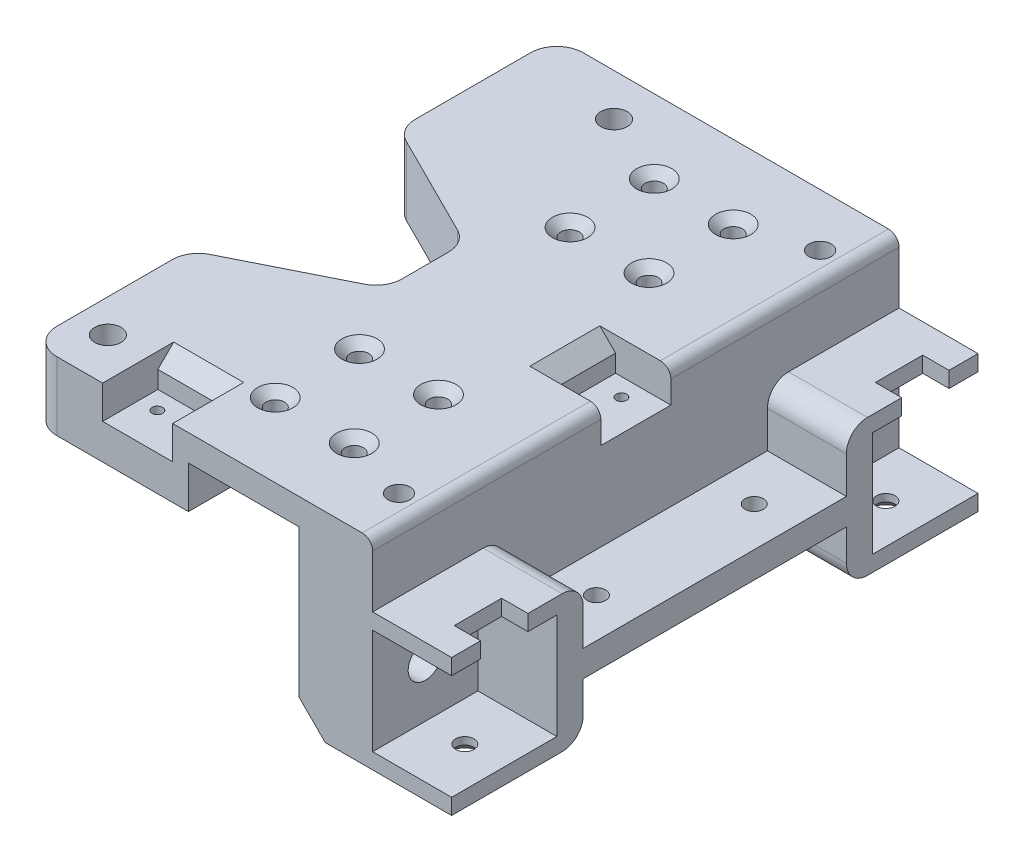
SolidWorks part; units mm, degrees
ref_plane "Front Plane" through (0, 0, 0) normal (0, 0, 1) x (1, 0, 0)
ref_plane "Top Plane" through (0, 0, 0) normal (0, 1, 0) x (1, 0, 0)
ref_plane "Right Plane" through (0, 0, 0) normal (1, 0, 0) x (0, 0, -1)
sketch "Sketch1" plane through (0, 0, 0) normal (0, 1, 0) x (1, 0, 0)
  line L0 (0, 50) -> (0, -50) construction
  line L1 (-10, 50) -> (10, 50)
  line L2 (-10, 50) -> (-10, -50)
  line L3 (-10, -50) -> (10, -50)
  line L4 (10, 50) -> (10, -50) construction
  line L5 (-10, 50) -> (10, -50) construction
  line L6 (-10, -50) -> (10, 50) construction
  line L7 (-7.5, 36) -> (7.5, 36) construction
  line L8 (-7.5, 36) -> (7.5, 20) construction
  line L9 (-10, 0) -> (10, 0) construction
  line L10 (-7.5, -36) -> (7.5, -20) construction
  line L11 (-7.5, -36) -> (7.5, -36) construction
  line L12 (-7.5, 20) -> (7.5, 20) construction
  line L13 (10, 50) -> (11, 50)
  line L14 (11, 50) -> (11, -50)
  line L15 (11, -50) -> (10, -50)
  circle A0 centre (-7.5, 36) radius 1.75
  circle A1 centre (7.5, 36) radius 1.75
  circle A2 centre (-7.5, 20) radius 1.75
  circle A3 centre (7.5, 20) radius 1.75
  circle A4 centre (7.5, -20) radius 1.75
  circle A5 centre (-7.5, -20) radius 1.75
  circle A6 centre (7.5, -36) radius 1.75
  circle A7 centre (-7.5, -36) radius 1.75
  point P0 (0, 0)
  point P16 (0, 36)
  dimension "D2" = 3.5
  dimension "D1" = 20
  dimension "D3" = 15
  dimension "D4" = 16
  dimension "D5" = 100
  dimension "D6" = 20
  dimension "D7" = 1
extrude "Boss-Extrude1" add sketch "Sketch1" along normal blind 5
sketch "Sketch2" plane through (11, 0, 0) normal (1, 0, 0) x (0, 0, -1)
  line L1 (-50, 5) -> (50, 5)
  line L2 (-50, 5) -> (-50, -33)
  line L3 (-50, -33) -> (50, -33)
  line L5 (50, 5) -> (50, -33)
  line L6 (50, 5) -> (50, 0) construction
  line L7 (-50, 5) -> (-50, 0) construction
  line L8 (-50, 5) -> (50, 5) construction
  dimension "D1" = 38
extrude "Boss-Extrude2" add sketch "Sketch2" along normal blind 14
sketch "Sketch3" plane through (25, 0, 0) normal (1, 0, 0) x (0, 0, -1)
  line L0 (0, 5) -> (0, -33) construction
  line L1 (-25, -18) -> (25, -18)
  line L2 (-25, -18) -> (-25, -23)
  line L3 (-25, -23) -> (25, -23)
  line L4 (25, -18) -> (25, -23)
  line L5 (50, 5) -> (-50, 5) construction
  line L6 (-50, -33) -> (50, -33) construction
  point P10 (0, -18)
  dimension "D1" = 5
  dimension "D2" = 50
  dimension "D3" = 10
extrude "Boss-Extrude3" add sketch "Sketch3" along normal blind 15
sketch "Sketch4" plane through (0, -18, 0) normal (0, 1, 0) x (1, 0, 0)
  line L0 (25, 0) -> (40, 0) construction
  line L1 (25, 25) -> (25, -25) construction
  line L2 (40, 25) -> (40, -25) construction
  line L3 (32.5, -15) -> (32.5, 15) construction
  circle A0 centre (32.5, 15) radius 1.75
  circle A1 centre (32.5, -15) radius 1.75
  point P8 (32.5, 0)
  dimension "D1" = 30
  dimension "D2" = 3.5
extrude "Cut-Extrude1" cut sketch "Sketch4" against normal through all
sketch "Sketch8" plane through (25, 0, 0) normal (1, 0, 0) x (0, 0, -1)
  line L0 (-50, 5) -> (-50, -33) construction
  line L1 (-50, -7) -> (-25, -7)
  line L2 (-50, -7) -> (-50, -10)
  line L3 (-50, -33) -> (-25, -33)
  line L4 (-25, -7) -> (-25, -33)
  line L5 (-50, -30) -> (-50, -33)
  line L6 (-50, -30) -> (-30, -30)
  line L8 (-50, -10) -> (-30, -10)
  line L9 (-30, -30) -> (-30, -10)
  line L10 (0, 20.9) -> (0, -20.9) construction
  line L11 (30, -30) -> (30, -10)
  line L12 (50, -10) -> (30, -10)
  line L13 (50, -30) -> (30, -30)
  line L14 (50, -30) -> (50, -33)
  line L15 (25, -7) -> (25, -33)
  line L16 (50, -33) -> (25, -33)
  line L17 (50, -7) -> (50, -10)
  line L18 (50, -7) -> (25, -7)
  line L19 (-50, -33) -> (50, -33) construction
  dimension "D1" = 3
  dimension "D2" = 5
  dimension "D3" = 3
  dimension "D4" = 20
  dimension "D5" = 20
extrude "Boss-Extrude6" add sketch "Sketch8" along normal blind 15
sketch "Sketch9" plane through (25, 0, 0) normal (1, 0, 0) x (0, 0, -1)
  line L0 (-50, -10) -> (-30, -30) construction
  line L1 (50, -10) -> (30, -30) construction
  circle A0 centre (-40, -20) radius 3.25
  circle A1 centre (40, -20) radius 3.25
  dimension "D1" = 6.5
extrude "Cut-Extrude3" cut sketch "Sketch9" against normal through all
sketch "Sketch10" plane through (11, 0, 0) normal (-1, 0, 0) x (0, 0, 1)
  circle A0 centre (-40, -20) radius 5.25
  circle A1 centre (40, -20) radius 5.25
  dimension "D1" = 10.5
extrude "Cut-Extrude4" cut sketch "Sketch10" against normal offset from surface (9 mm away) 5 up to face at (25, -20, 36.75)
sketch "Sketch11" plane through (0, -7, 0) normal (0, 1, 0) x (1, 0, 0)
  line L0 (40, -25) -> (40, -50) construction
  line L1 (40, -35.5) -> (35, -35.5)
  line L2 (40, -35.5) -> (40, -44.5)
  line L3 (40, -44.5) -> (35, -44.5)
  line L4 (35, -35.5) -> (35, -44.5)
  line L5 (35, -40) -> (40, -40) construction
  line L6 (40, -50) -> (25, -50) construction
  line L7 (-10, 0) -> (40, 0) construction
  line L8 (-10, 50) -> (-10, -50) construction
  line L9 (40, 25) -> (40, -25) construction
  line L10 (40, -35.5) -> (35, -35.5)
  line L11 (40, -44.5) -> (35, -44.5)
  line L12 (35, 40) -> (40, 40) construction
  line L13 (40, 44.5) -> (35, 44.5)
  line L14 (40, 35.5) -> (35, 35.5)
  line L15 (35, 35.5) -> (35, 44.5)
  line L16 (40, 44.5) -> (35, 44.5)
  line L17 (40, 35.5) -> (40, 44.5)
  line L18 (40, 35.5) -> (35, 35.5)
  line M7 (40, -50) -> (40, -25)
  dimension "D1" = 9
  dimension "D2" = 10
  dimension "D3" = 5
extrude "Cut-Extrude5" cut sketch "Sketch11" against normal up to next contours L1 L4 L3 M7 | L14 L17 L13 L15 region at (37.5, -7, 40) region at (37.5, -7, -40)
sketch "Sketch12" plane through (0, -30, 0) normal (0, 1, 0) x (1, 0, 0)
  line L0 (40, -40) -> (25, -40) construction
  line L1 (40, -30) -> (40, -50) construction
  line L2 (25, -25) -> (25, -50) construction
  line L3 (-20.9, 0) -> (20.9, 0) construction
  circle A0 centre (32.5, -40) radius 1.75
  circle A2 centre (32.5, 40) radius 1.75
  dimension "D1" = 3.5
extrude "Cut-Extrude6" cut sketch "Sketch12" against normal through all
sketch "Sketch13" plane through (-10, 0, 0) normal (-1, 0, 0) x (0, 0, 1)
  line L1 (-50, 5) -> (50, 5)
  line L2 (-50, 5) -> (-50, -8)
  line L3 (-50, -8) -> (50, -8)
  line L4 (50, 5) -> (50, -8)
  dimension "D1" = 13
extrude "Boss-Extrude7" add sketch "Sketch13" along normal blind 30
sketch "Sketch14" plane through (0, 5, 0) normal (0, 1, 0) x (1, 0, 0)
  line L6 (-27.65, 42) -> (-27.65, -41.58) construction
  line L12 (-21.15, 35.5) -> (40, 35.5) construction
  line L18 (-33.73, -35.5) -> (40, -35.5) construction
  circle A0 centre (-21.15, 42) radius 2.5
  circle A1 centre (-33.73, -41.58) radius 2.5
  circle A2 centre (-33.73, -41.58) radius 6.08 construction
  circle A3 centre (-21.15, 42) radius 6.5 construction
  dimension "D1" = 5
  dimension "D2" = 5
  dimension "D4" = 12.16
  dimension "D5" = 13
  dimension "D3" = 21.15
extrude "Cut-Extrude7" cut sketch "Sketch14" against normal through all
sketch "Sketch15" plane through (0, -8, 0) normal (0, -1, 0) x (1, 0, 0)
  line L0 (-40, -50) -> (-40, 50) construction
  line L1 (-29.63, 43.9471) -> (-33.73, 46.3143)
  line L2 (-33.73, 46.3143) -> (-37.83, 43.9471)
  line L3 (-37.83, 43.9471) -> (-37.83, 39.2129)
  line L4 (-37.83, 39.2129) -> (-33.73, 36.8457)
  line L5 (-33.73, 36.8457) -> (-29.63, 39.2129)
  line L6 (-29.63, 39.2129) -> (-29.63, 43.9471)
  line L7 (-17.05, -44.3671) -> (-17.05, -39.6329)
  line L8 (-17.05, -39.6329) -> (-21.15, -37.2657)
  line L9 (-21.15, -37.2657) -> (-25.25, -39.6329)
  line L10 (-25.25, -39.6329) -> (-25.25, -44.3671)
  line L11 (-25.25, -44.3671) -> (-21.15, -46.7343)
  line L12 (-21.15, -46.7343) -> (-17.05, -44.3671)
  circle A0 centre (-33.73, 41.58) radius 4.1 construction
  circle A1 centre (-21.15, -42) radius 4.1 construction
  dimension "D1" = 8.2
extrude "Cut-Extrude8" cut sketch "Sketch15" against normal blind 5
sketch "Sketch16" plane through (0, 5, 0) normal (0, 1, 0) x (1, 0, 0)
  line L0 (20, 40) -> (40, 40) construction
  line L1 (40, 40) -> (40, -40) construction
  line L2 (40, -40) -> (20, -40) construction
  line L3 (20, -40) -> (20, 40) construction
  line L4 (40, 50) -> (40, 30) construction
  line L5 (40, -30) -> (40, -50) construction
  circle A0 centre (20, 40) radius 2.1
  circle A1 centre (20, -40) radius 2.1
  dimension "D1" = 4.2
  dimension "D2" = 4.2
  dimension "D3" = 20
extrude "Cut-Extrude9" cut sketch "Sketch16" against normal blind 4
chamfer "Chamfer1" distance 1.6 angle 45 8 edges at (7.5, 5, 34.25) (-7.5, 5, 34.25) (7.5, 5, 18.25) (-7.5, 5, 18.25) (7.5, 5, -18.25) (-7.5, 5, -18.25) (7.5, 5, -34.25) (-7.5, 5, -34.25)
sketch "Sketch17" plane through (0, 5, 0) normal (0, 1, 0) x (1, 0, 0)
  line L0 (-40, 20) -> (-15, 7.5)
  line L1 (-40, -50) -> (-40, 50) construction
  line L2 (-15, 7.5) -> (-15, -7.5)
  line L3 (-15, -7.5) -> (-40, -20)
  line L4 (-40, -20) -> (-40, 20)
  point P5 (-15, 0)
  dimension "D1" = 15
  dimension "D2" = 25
  dimension "D3" = 40
extrude "Cut-Extrude10" cut sketch "Sketch17" against normal through all
chamfer "Chamfer2" distance 1.6 angle 45 2 edges at (32.5, -33, -41.75) (32.5, -33, 41.75)
chamfer "Chamfer3" distance 5 angle 45 1 edges at (11, -33, 0)
sketch "Sketch18" plane through (0, 1, 0) normal (0, 1, 0) x (1, 0, 0)
  circle A0 centre (20, 40) radius 1.75
  circle A1 centre (20, -40) radius 1.75
  dimension "D1" = 3.5
  dimension "D2" = 3.5
extrude "Cut-Extrude11" cut sketch "Sketch18" against normal blind 4
fillet "Fillet1" radius 5 6 edges at (-40, -1.5, 50) (-40, -1.5, 20) (-15, -1.5, 7.5) (-15, -1.5, -7.5) (-40, -1.5, -20) (-40, -1.5, -50)
fillet "Fillet2" radius 4 4 edges at (32.5, -33, -25) (32.5, -7, -25) (32.5, -33, 25) (32.5, -7, 25)
sketch "Sketch19" plane through (25, 0, 0) normal (1, 0, 0) x (0, 0, -1)
  line L0 (50, 5) -> (-50, 5) construction
  line L1 (-6.65, 5) -> (6.65, 5)
  line L2 (-6.65, 5) -> (-6.65, -1.3)
  line L3 (-6.65, -1.3) -> (6.65, -1.3)
  line L4 (6.65, 5) -> (6.65, -1.3)
  point P7 (0, 5)
  dimension "D1" = 13.3
  dimension "D2" = 6.3
extrude "Cut-Extrude12" cut sketch "Sketch19" against normal blind 10.5
sketch "Sketch20" plane through (0, -1.3, 0) normal (0, 1, 0) x (1, 0, 0)
  line L0 (19, 3.25) -> (19, -3.25) construction
  line L3 (14.5, 6.65) -> (14.5, -6.65) construction
  line L4 (18, 3.25) -> (18, -3.25) construction
  circle A0 centre (19, 3.25) radius 1
  circle A1 centre (19, -3.25) radius 1
  point P2 (14.5, 0)
  point P3 (19, 0)
  dimension "D1" = 2
  dimension "D2" = 6.5
  dimension "D3" = 3.5
extrude "Cut-Extrude13" cut sketch "Sketch20" against normal blind 3
chamfer "Chamfer4" distance 3 angle 45 1 edges at (14.5, 5, 0)
fillet "Fillet3" radius 2 2 edges at (25, 5, -28.325) (25, 5, 28.325)
sketch "Sketch22" plane through (0, 5, 0) normal (0, 1, 0) x (1, 0, 0)
  line L0 (-35, -50) -> (23, -50) construction
  line L1 (-26.3, -50) -> (-13, -50)
  line L2 (-26.3, -50) -> (-26.3, -39.5)
  line L3 (-26.3, -39.5) -> (-13, -39.5)
  line L4 (-13, -50) -> (-13, -39.5)
  line L5 (-10, 50) -> (-10, -50) construction
  dimension "D1" = 10.5
  dimension "D2" = 13.3
  dimension "D3" = 3
extrude "Cut-Extrude14" cut sketch "Sketch22" against normal blind 6.3
sketch "Sketch23" plane through (0, -1.3, 0) normal (0, 1, 0) x (1, 0, 0)
  line L0 (-22.9, -43) -> (-16.4, -43) construction
  line L1 (-13, -39.5) -> (-26.3, -39.5) construction
  line L2 (-26.3, -50) -> (-13, -50) construction
  circle A0 centre (-22.9, -43) radius 1
  circle A1 centre (-16.4, -43) radius 1
  point P9 (-19.65, -50)
  point P10 (-19.65, -43)
  dimension "D1" = 2
  dimension "D2" = 2
  dimension "D3" = 6.5
  dimension "D4" = 3.5
extrude "Cut-Extrude15" cut sketch "Sketch23" against normal blind 3
chamfer "Chamfer5" distance 3 angle 45 1 edges at (-19.65, 5, 39.5)
